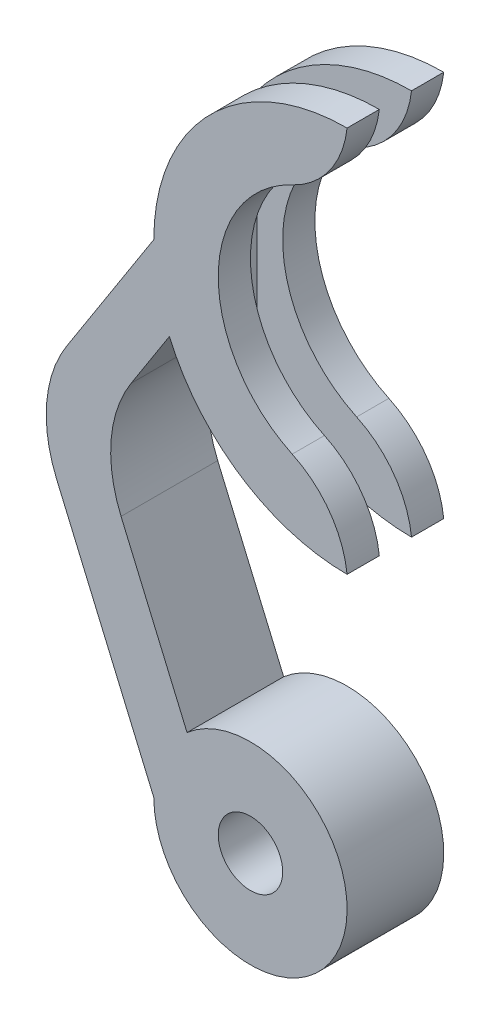
SolidWorks part; units mm, degrees
ref_plane "Front Plane" through (0, 0, 0) normal (0, 0, 1) x (1, 0, 0)
ref_plane "Top Plane" through (0, 0, 0) normal (0, 1, 0) x (1, 0, 0)
ref_plane "Right Plane" through (0, 0, 0) normal (1, 0, 0) x (0, 0, -1)
sketch "Sketch1" plane through (0, 0, 0) normal (0, 0, 1) x (1, 0, 0)
  line L0 (0, 0) -> (0, -120) construction
  line L1 (0, 0) -> (0, -10)
  line L2 (0, -50) -> (0, -60)
  line L4 (-30, -30) -> (-49.2547, -60)
  line L5 (-49.2547, -60) -> (-30, -105)
  line L6 (-20, -30) -> (-39.2547, -60)
  line L7 (-39.2547, -60) -> (-20, -105)
  line L8 (-30, -30) -> (-20, -30)
  line L9 (-30, -105) -> (-20, -105)
  arc A0 (0, -10) -> (0, -50) centre (0, -30) ccw
  arc A1 (0, 0) -> (0, -60) centre (0, -30) ccw
  circle A2 centre (-15, -105) radius 15
  circle A3 centre (-15, -105) radius 5
  dimension "D1" = 40
  dimension "D2" = 60
  dimension "D5" = 15
  dimension "D6" = 15
  dimension "D4" = 120
  dimension "D7" = 10
  dimension "D8" = 15
extrude "Boss-Extrude1" add sketch "Sketch1" along normal blind 15 contours L8 A1 L6 | L1 A1 L8 A0 | L6 A1 L2 A0 | A2 L7 L6 A1 L4 L5 | L7 A2 L9 | L7 A3 L9 A2 region at (-16.1277, -13.8723, 0) region at (-36.5183, -67.2913, 0) region at (-26.1035, -34.0913, 0) region at (-14.1866, -48.4697, 0) region at (-25.4415, -100.8757, 0) region at (-25, -105.4243, 0)
fillet "Fillet1" radius 20 2 edges at (-39.2547, -60, 7.5) (-49.2547, -60, 7.5)
fillet "Fillet2" radius 15 2 edges at (0, -50, 7.5) (0, -10, 7.5)
sketch "Sketch2" plane through (0, 0, 0) normal (1, 0, 0) x (0, 0, -1)
  line L0 (-15, 0) -> (0, 0) construction
  line L1 (-10, 0) -> (-5, 0)
  line L2 (-10, 0) -> (-10, -60)
  line L3 (-10, -60) -> (-5, -60)
  line L4 (-5, 0) -> (-5, -60)
  line L5 (-15, -60) -> (0, -60) construction
  line L6 (0, -48.0952) -> (0, -11.9048) construction
  dimension "D1" = 5
  dimension "D2" = 5
extrude "Cut-Extrude1" cut sketch "Sketch2" against normal blind 24
